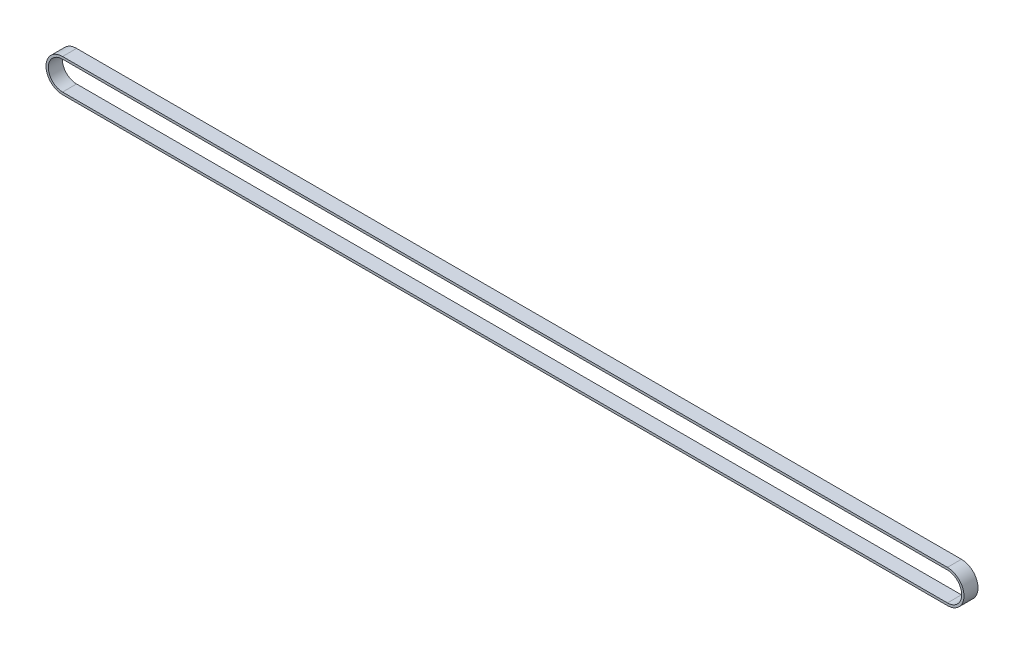
SolidWorks part; units mm, degrees
ref_plane "Front Plane" through (0, 0, 0) normal (0, 0, 1) x (1, 0, 0)
ref_plane "Top Plane" through (0, 0, 0) normal (0, 1, 0) x (1, 0, 0)
ref_plane "Right Plane" through (0, 0, 0) normal (1, 0, 0) x (0, 0, -1)
sketch "Sketch2" plane through (0, 0, 0) normal (0, 0, 1) x (1, 0, 0)
  line L0 (189.55, -6.1) -> (0, -6.1)
  line L1 (0, 6.1) -> (189.55, 6.1)
  line L2 (189.55, 6.1) -> (189.55, -6.1) construction
  arc A0 (0, -6.1) -> (0, 6.1) centre (0, 0) cw
  dimension "D1" = 6.1
  dimension "D2" = 189.55
extrude "Extrude-Thin1" add sketch "Sketch2" along normal blind 6 thin thin type one direction reverse wall 1
mirror "Mirror1" about plane through (189.55, 7.1, 6) normal (1, 0, 0) of "Extrude-Thin1"
equation "\"D2@Sketch2\"= 379.1 / 2"
